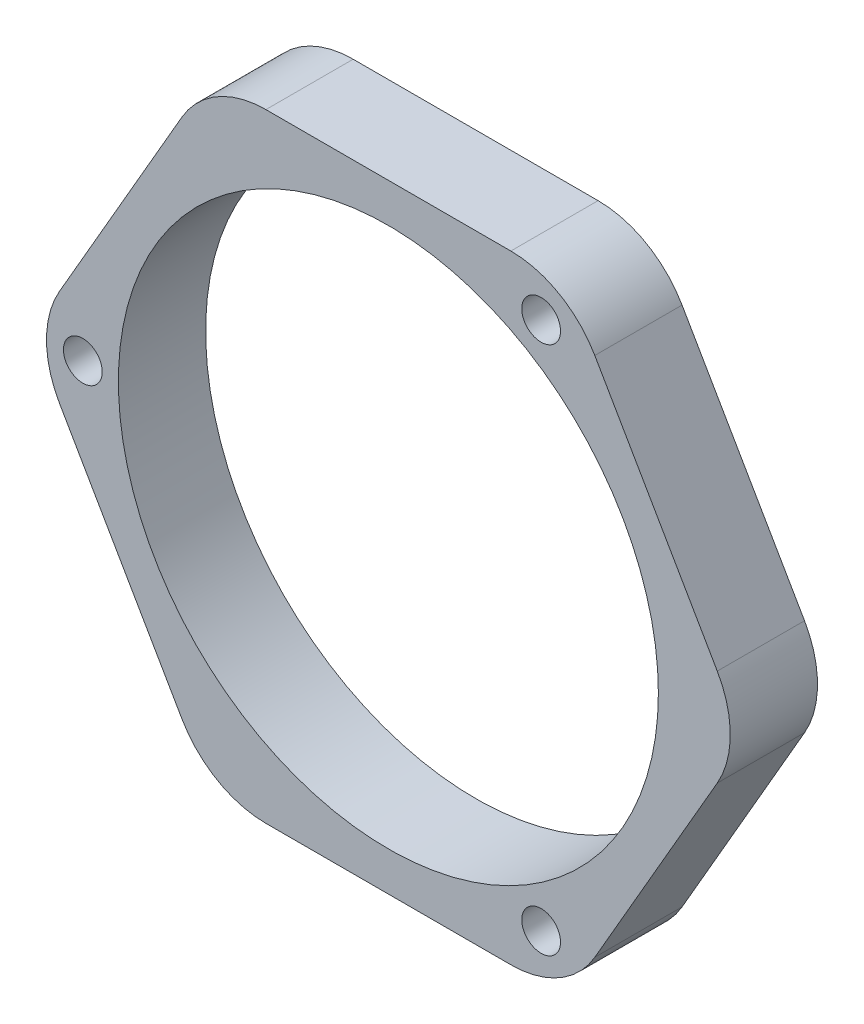
SolidWorks part; units mm, degrees
ref_plane "Front Plane" through (0, 0, 0) normal (0, 0, 1) x (1, 0, 0)
ref_plane "Top Plane" through (0, 0, 0) normal (0, 1, 0) x (1, 0, 0)
ref_plane "Right Plane" through (0, 0, 0) normal (1, 0, 0) x (0, 0, -1)
sketch "Sketch1" plane through (0, 0, 0) normal (0, 0, 1) x (1, 0, 0)
  line L1 (18.4059, -31.88) -> (36.8119, 0)
  line L2 (36.8119, 0) -> (18.4059, 31.88)
  line L3 (18.4059, 31.88) -> (-18.4059, 31.88)
  line L4 (-18.4059, 31.88) -> (-36.8119, 0)
  line L5 (-36.8119, 0) -> (-18.4059, -31.88)
  line L6 (-18.4059, -31.88) -> (18.4059, -31.88)
  circle A0 centre (0, 0) radius 27.85
  circle A1 centre (0, 0) radius 31.88 construction
  dimension "D1" = 63.76
  dimension "D2" = 55.7
extrude "Boss-Extrude1" add sketch "Sketch1" along normal blind 9
fillet "Fillet1" radius 10 6 edges at (-18.4059, -31.88, 4.5) (18.4059, -31.88, 4.5) (-36.8119, 0, 4.5) (36.8119, 0, 4.5) (18.4059, 31.88, 4.5) (-18.4059, 31.88, 4.5)
sketch "Sketch3" plane through (0, 0, 9) normal (0, 0, 1) x (1, 0, 0)
  line L0 (0, 0) -> (-35.2648, 0) construction
  arc A0 (-33.9251, 5) -> (-33.9251, -5) centre (-25.2648, 0) ccw construction
  circle A1 centre (-31.5148, 0) radius 3.75 construction
  circle A2 centre (-31.5148, 0) radius 2
  dimension "D1" = 7.5
  dimension "D2" = 4
extrude "Cut-Extrude1" cut sketch "Sketch3" against normal through all contours A2
pattern_circular "CirPattern1" count 3 over 360 about axis through (0, 0, 9) along (0, 0, 1) of "Cut-Extrude1"
equation "\"Depth\" = 9mm"
equation "\"de\"=5"
equation "\"D1@Boss-Extrude1\"=\"Depth\""
